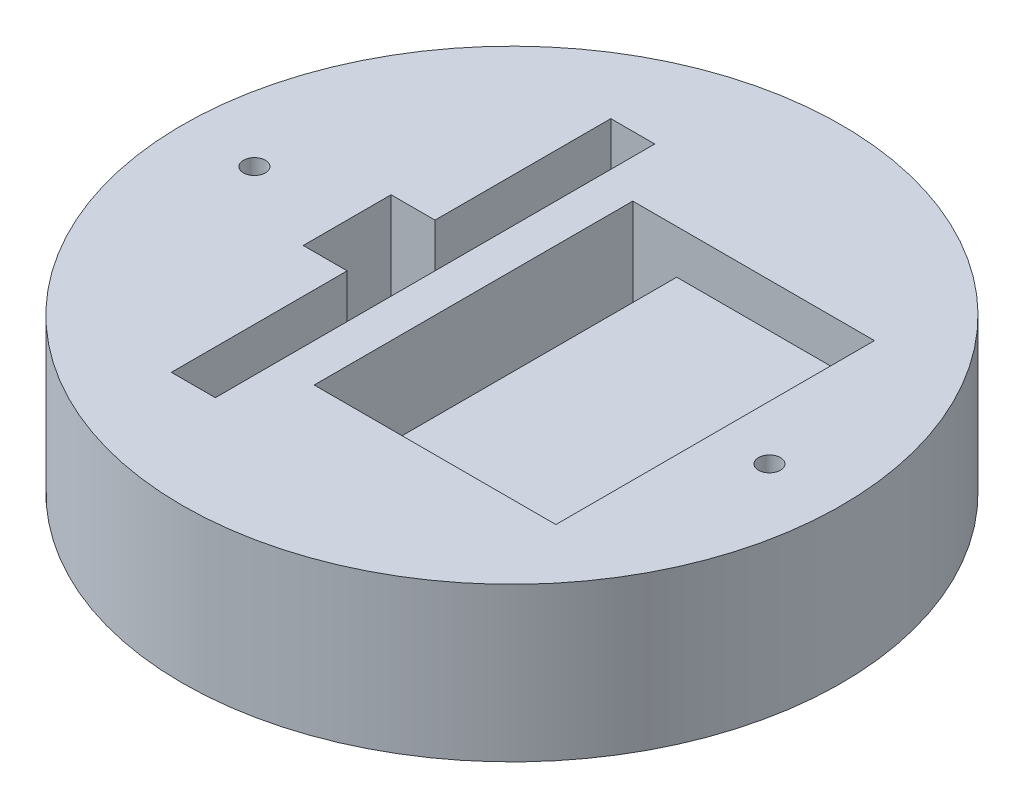
SolidWorks part; units mm, degrees
ref_plane "Спереди" through (0, 0, 0) normal (0, 0, 1) x (1, 0, 0)
ref_plane "Сверху" through (0, 0, 0) normal (0, 1, 0) x (1, 0, 0)
ref_plane "Справа" through (0, 0, 0) normal (1, 0, 0) x (0, 0, -1)
sketch "Эскиз3" plane through (0, 0, 0) normal (0, 1, 0) x (1, 0, 0)
  circle A0 centre (0, 0) radius 15
extrude "Бобышка-Вытянуть2" add sketch "Эскиз3" along normal blind 7
sketch "Эскиз8" plane through (0, 7, 0) normal (0, 1, 0) x (1, 0, 0)
  line L0 (0, 21.5769) -> (0, -20.9711) construction
  line L11 (-23.6577, 0) -> (29.9171, 0) construction
  line L30 (-5.5, 10) -> (-3.5, 10)
  line L32 (-5.5, -10) -> (-3.5, -10)
  line L33 (-3.5, 10) -> (-3.5, -10)
  line L34 (-5.5, 2) -> (-7.5, 2)
  line L36 (-5.5, -2) -> (-7.5, -2)
  line L37 (-7.5, 2) -> (-7.5, -2)
  line L40 (-5.5, 10) -> (-5.5, 2)
  line L42 (-5.5, -10) -> (-5.5, -2)
  point P0 (-3.5, 0)
  point P27 (0, 0)
  dimension "D1" = 3.5
  dimension "D2" = 2
  dimension "D3" = 4
  dimension "D7" = 2
  dimension "D8" = 20
extrude "Вырез-Вытянуть1" cut sketch "Эскиз8" against normal through all
sketch "Эскиз10" plane through (0, 7, 0) normal (0, 1, 0) x (1, 0, 0)
  line L0 (-1.75, 7.25) -> (-1.75, -7.25)
  line L5 (-50, 0) -> (50, 0) construction
  line L10 (-1.75, -7.25) -> (9.25, -7.25)
  line L12 (-1.75, 7.25) -> (9.25, 7.25)
  line L13 (9.25, -7.25) -> (9.25, 7.25)
  line L14 (-1.75, -7.25) -> (9.25, 7.25) construction
  line L15 (-1.75, 7.25) -> (9.25, -7.25) construction
  point P0 (3.75, 0)
  dimension "D1" = 14.5
  dimension "D2" = 11
extrude "Вырез-Вытянуть2" cut sketch "Эскиз10" against normal blind 2
sketch "Эскиз11" plane through (0, 5, 0) normal (0, 1, 0) x (1, 0, 0)
  line L4 (0.25, 7.25) -> (0.25, -7.25)
  line L5 (-1.75, -7.25) -> (9.25, -7.25) construction
  line L10 (0.25, 7.25) -> (-1.75, 7.25)
  line L11 (-1.75, 7.25) -> (-1.75, -7.25)
  line L12 (-1.75, -7.25) -> (0.25, -7.25)
  dimension "D1" = 2
extrude "Вырез-Вытянуть3" cut sketch "Эскиз11" against normal through all
sketch "Эскиз16" plane through (0, 7, 0) normal (0, 1, 0) x (1, 0, 0)
  line L1 (-14.6906, 3.0309) -> (-8.75, 3.0309)
  line L2 (0, 16.6744) -> (0, -16.2444) construction
  line L3 (-24.5606, 0) -> (23.8804, 0) construction
  line L4 (-14.6906, -3.0309) -> (-8.75, -3.0309)
  line L5 (-8.75, 3.0309) -> (-8.75, -3.0309)
  line L6 (8.75, 3.0309) -> (8.75, -3.0309)
  line L7 (14.6906, -3.0309) -> (8.75, -3.0309)
  line L8 (14.6906, 3.0309) -> (8.75, 3.0309)
  line L9 (-14.6906, 3.0309) -> (-14.6906, -3.0309)
  line L10 (-14.6906, 3.0309) -> (-8.75, -3.0309) construction
  line L11 (-14.6906, -3.0309) -> (-8.75, 3.0309) construction
  circle A0 centre (0, 0) radius 15 construction
  arc A1 (-14.6906, 3.0309) -> (-14.6906, -3.0309) centre (0, 0) ccw
  arc A2 (14.6906, 3.0309) -> (14.6906, -3.0309) centre (0, 0) cw
  circle A3 centre (-11.7203, 0) radius 0.5
  dimension "D2" = 1
  dimension "D3" = 11.7203
  dimension "D1" = 5.9406
sketch "Эскиз17" plane through (0, 7, 0) normal (0, 1, 0) x (1, 0, 0)
  line L0 (0, 16.6744) -> (0, -16.2444) construction
  line L1 (0, 11.8289) -> (0, -10.3938) construction
  circle A0 centre (-11.7203, 0) radius 0.5 construction
  circle A1 centre (-11.7203, 0) radius 0.5
  circle A2 centre (11.7203, 0) radius 0.5
extrude "Вырез-Вытянуть4" cut sketch "Эскиз17" against normal through all
